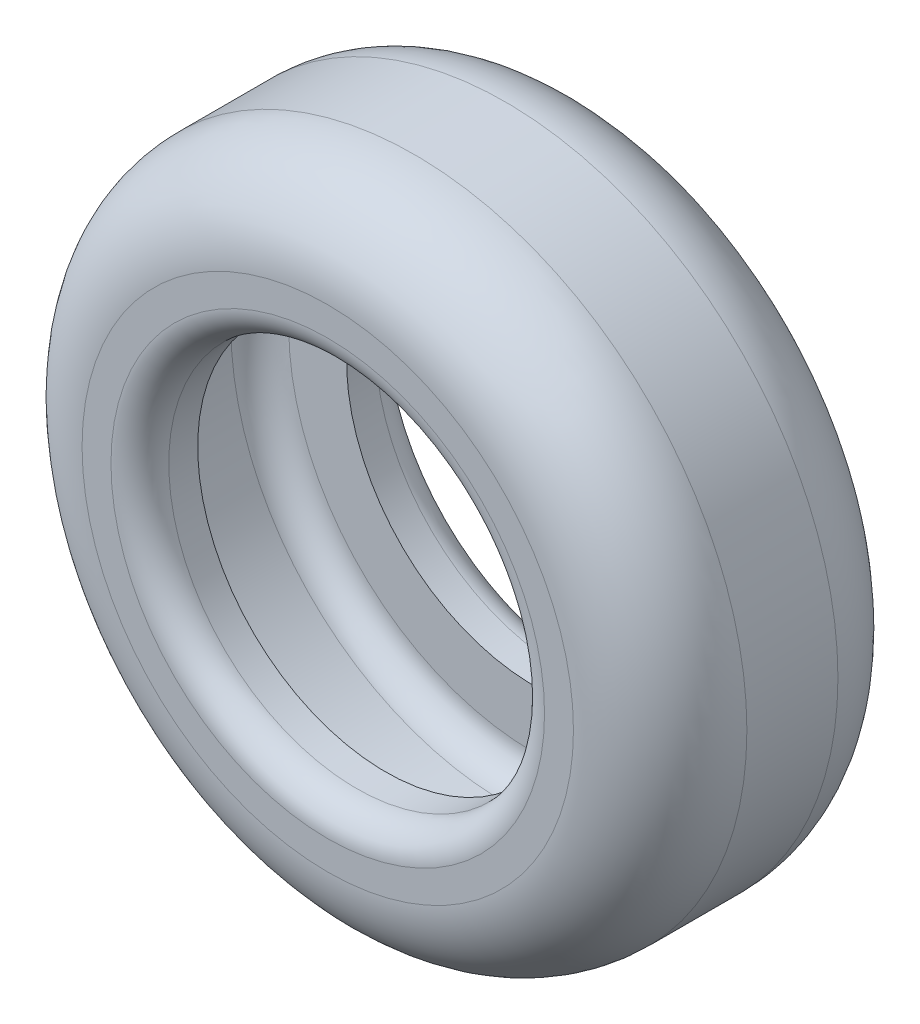
SolidWorks part; units mm, degrees
ref_plane "Front Plane" through (0, 0, 0) normal (0, 0, 1) x (1, 0, 0)
ref_plane "Top Plane" through (0, 0, 0) normal (0, 1, 0) x (1, 0, 0)
ref_plane "Right Plane" through (0, 0, 0) normal (1, 0, 0) x (0, 0, -1)
sketch "Sketch1" plane through (0, 0, 0) normal (0, 0, 1) x (1, 0, 0)
  circle A0 centre (0, 0) radius 165.1
  dimension "D1" = 330.2
extrude "Extrude-Thin1" add sketch "Sketch1" along normal blind 232.41 thin thin type one direction wall 127
fillet "Fillet1" radius 76.2 2 edges at (292.1, 0, 0) (292.1, 0, 232.41)
fillet "Fillet2" radius 25.4 2 edges at (165.1, 0, 232.41) (165.1, 0, 0)
shell "Shell1" thickness 50.8 removed face at (165.1, 0, 207.01)
